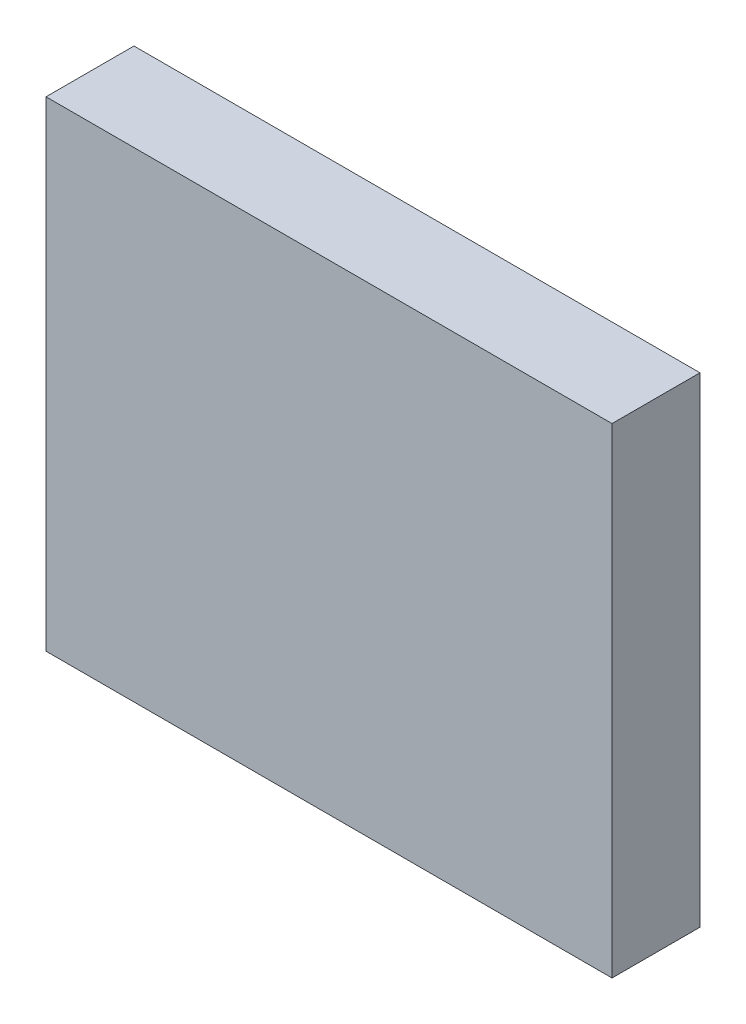
SolidWorks part; units mm, degrees
ref_plane "Front Plane" through (0, 0, 0) normal (0, 0, 1) x (1, 0, 0)
ref_plane "Top Plane" through (0, 0, 0) normal (0, 1, 0) x (1, 0, 0)
ref_plane "Right Plane" through (0, 0, 0) normal (1, 0, 0) x (0, 0, -1)
sketch "Sketch1" plane through (0, 0, 0) normal (0, 0, 1) x (1, 0, 0)
  line L1 (0, 0) -> (128.7083, 0)
  line L2 (0, 0) -> (0, 109.191)
  line L3 (0, 109.191) -> (128.7083, 109.191)
  line L4 (128.7083, 0) -> (128.7083, 109.191)
extrude "Boss-Extrude1" add sketch "Sketch1" along normal blind 20
